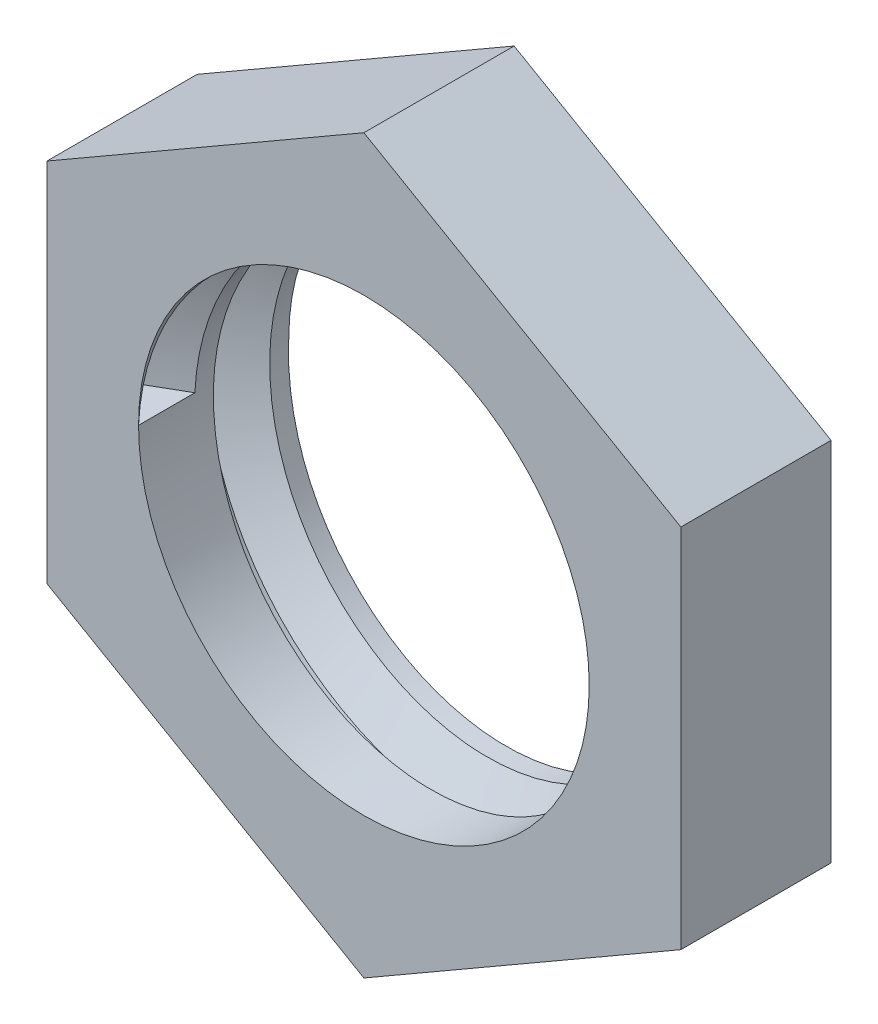
SolidWorks part; units mm, degrees
ref_plane "Front Plane" through (0, 0, 0) normal (0, 0, 1) x (1, 0, 0)
ref_plane "Top Plane" through (0, 0, 0) normal (0, 1, 0) x (1, 0, 0)
ref_plane "Right Plane" through (0, 0, 0) normal (1, 0, 0) x (0, 0, -1)
sketch "Sketch1" plane through (0, 0, 0) normal (0, 0, 1) x (1, 0, 0)
  line L1 (-4.22, -2.4364) -> (0, -4.8728)
  line L2 (0, -4.8728) -> (4.22, -2.4364)
  line L3 (4.22, -2.4364) -> (4.22, 2.4364)
  line L4 (4.22, 2.4364) -> (0, 4.8728)
  line L5 (0, 4.8728) -> (-4.22, 2.4364)
  line L6 (-4.22, 2.4364) -> (-4.22, -2.4364)
  circle A0 centre (0, 0) radius 4.22 construction
  circle A1 centre (0, 0) radius 3
  dimension "D1" = 8.44
  dimension "D2" = 6
extrude "Boss-Extrude1" add sketch "Sketch1" along normal blind 2
thread "Thread1" pitch 1 method cut profile "Thread Profile1" start angle 0, offset 0, length 0, pitch 1, diameter 6
ref_plane "Plane1" through (-3, 0, 2) normal (0, -1, 0) x (-1, 0, 0)
sketch "Thread Profile1" plane through (-3, 0, 2) normal (0, -1, 0) x (-1, 0, 0)
  line L0 (0, 0) -> (0, 1) construction
  line L1 (0, 0) -> (0.5413, 0.3125)
  line L2 (0.5413, 0.3125) -> (0.5413, 0.4375)
  line L3 (0.5413, 0.4375) -> (0, 0.75)
  line L4 (0.5413, 0.375) -> (0, 0.375) construction
  line L11 (0, 0) -> (0, 0.75)
  point P2 (0, 0)
  dimension "Pitch" = 1
  dimension "Profile_Angle" = 60
  dimension "Profile_Land" = 0.125
  dimension "Profile_Height" = 0.5413
